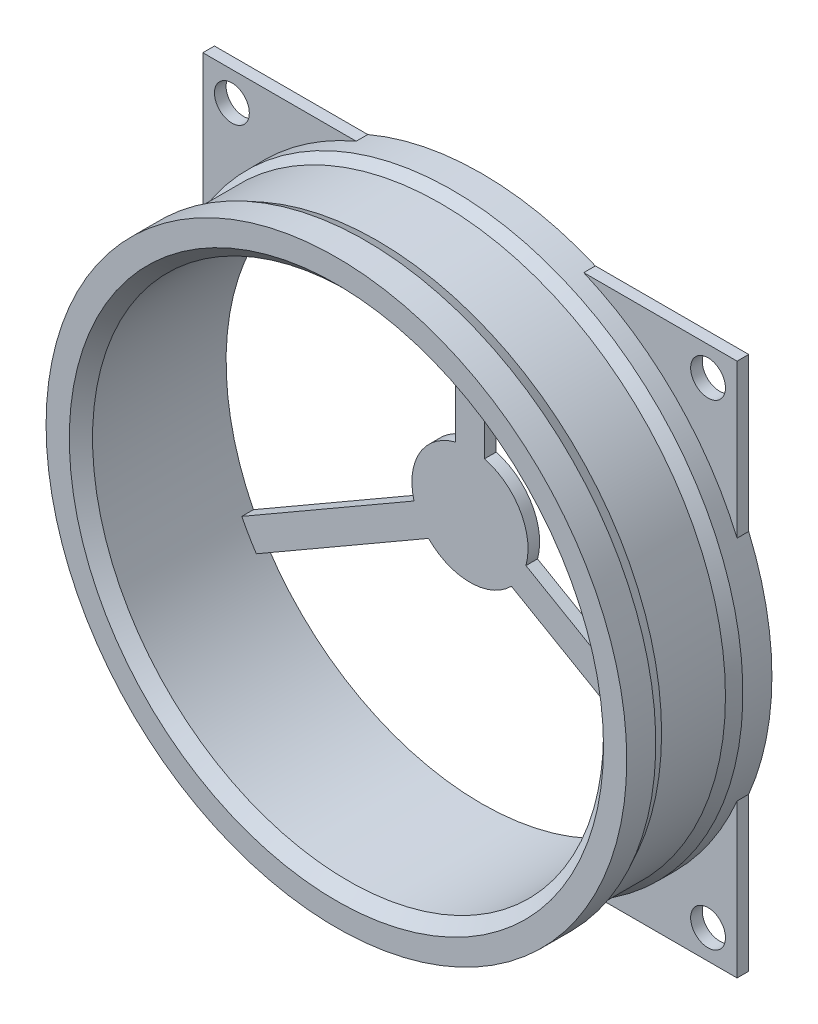
SolidWorks part; units mm, degrees
ref_plane "Alzado" through (0, 0, 0) normal (0, 0, 1) x (1, 0, 0)
ref_plane "Planta" through (0, 0, 0) normal (0, 1, 0) x (1, 0, 0)
ref_plane "Vista lateral" through (0, 0, 0) normal (1, 0, 0) x (0, 0, -1)
sketch "Croquis1" plane through (0, 0, 0) normal (0, 0, 1) x (1, 0, 0)
  line L0 (-46, -19.5959) -> (-46, -46)
  line L1 (-46, 46) -> (-19.5959, 46)
  line L2 (-46, 46) -> (-46, 19.5959)
  line L3 (-46, -46) -> (-19.5959, -46)
  line L4 (46, 46) -> (46, 19.5959)
  line L5 (-46, 46) -> (46, -46) construction
  line L6 (-46, -46) -> (46, 46) construction
  line L7 (19.5959, -46) -> (46, -46)
  line L8 (46, -19.5959) -> (46, -46)
  line L9 (19.5959, 46) -> (46, 46)
  line L10 (0, 0) -> (0, 44) construction
  line L11 (-2.5, 9.6825) -> (-2.5, 43.9289)
  line L12 (2.5, 9.6825) -> (2.5, 43.9289)
  line L13 (9.6353, -2.6762) -> (39.2936, -19.7994)
  line L14 (7.1353, -7.0063) -> (36.7936, -24.1295)
  line L15 (-7.1353, -7.0063) -> (-36.7936, -24.1295)
  line L16 (-9.6353, -2.6762) -> (-39.2936, -19.7994)
  circle A1 centre (0, 0) radius 50
  circle A2 centre (0, 0) radius 44
  circle A3 centre (0, 0) radius 10
  point P0 (0, 0)
  point P33 (0, 0)
  dimension "D2" = 100
  dimension "D4" = 88
  dimension "D5" = 20
  dimension "D1" = 92
  dimension "D3" = 92
  dimension "D6" = 2.5
  dimension "D7" = 5
  dimension "D8" = 3
extrude "Saliente-Extruir2" add sketch "Croquis1" along normal blind 2 contours A1 L1 L2 | A1 L0 L3 | A1 L7 L8 | A1 L4 L9 | A3 | A3 L12 A2 L11 | A3 L16 A2 L15 | A3 L14 A2 L13 region at (-38.3856, -38.3856, 0) region at (-38.3856, 38.3856, 0) region at (38.3856, -38.3856, 0) region at (38.3856, 38.3856, 0) region at (0, 26.9354, 0) region at (0, 0, 0) region at (-23.3268, -13.4677, 0) region at (23.3268, -13.4677, 0)
extrude "Saliente-Extruir3" add sketch "Croquis1<5>" along normal blind 25 contours A1 A2 region at (-48.5858, 0, 0)
sketch "Croquis1<5>" plane through (0, 0, 0) normal (0, 0, 1) x (1, 0, 0) same geometry as "Croquis1"
sketch "Croquis2" plane through (0, 0, 0) normal (1, 0, 0) x (0, 0, -1)
  line L0 (0, 0) -> (0, 50) construction
  line L1 (0, 50) -> (-5, 50) construction
  line L2 (0, 50) -> (-25, 50) construction
  line L3 (-5, 50) -> (-20, 50)
  line L4 (-12.5, 50) -> (-12.5, 49) construction
  line L5 (-18, 49) -> (-7, 49)
  line L6 (-7, 49) -> (-5, 50)
  line L7 (-18, 49) -> (-20, 50)
  point P14 (-12.5, 49)
  dimension "D1" = 5
  dimension "D2" = 5
  dimension "D3" = 1
  dimension "D4" = 18
ref_axis "Eje1" through (0, 0, -1.25) along (0, 0, 1)
revolve "Cortar-Revolución1" cut sketch "Croquis2" angle 360 about axis through (0, 0, -1.25) along (0, 0, 1)
chamfer "Chaflán1" distance 2 angle 45 1 edges at (44, 0, 25)
sketch "Croquis3" plane through (0, 0, 2) normal (0, 0, 1) x (1, 0, 0)
  line L1 (-41, -41) -> (41, -41) construction
  line L2 (-41, -41) -> (-41, 41) construction
  line L3 (-41, 41) -> (41, 41) construction
  line L4 (41, -41) -> (41, 41) construction
  line L5 (-41, -41) -> (41, 41) construction
  line L6 (-41, 41) -> (41, -41) construction
  circle A1 centre (-41, 41) radius 3
  circle A2 centre (-41, -41) radius 3
  circle A3 centre (41, 41) radius 3
  circle A4 centre (41, -41) radius 3
  point P0 (0, 0)
  dimension "D3" = 6
  dimension "D4" = 6
  dimension "D5" = 6
  dimension "D6" = 6
  dimension "D1" = 82
  dimension "D2" = 82
extrude "Cortar-Extruir1" cut sketch "Croquis3" against normal blind 25
equation "\"D4@Croquis1\"=\"D1@Croquis1\"-4"
